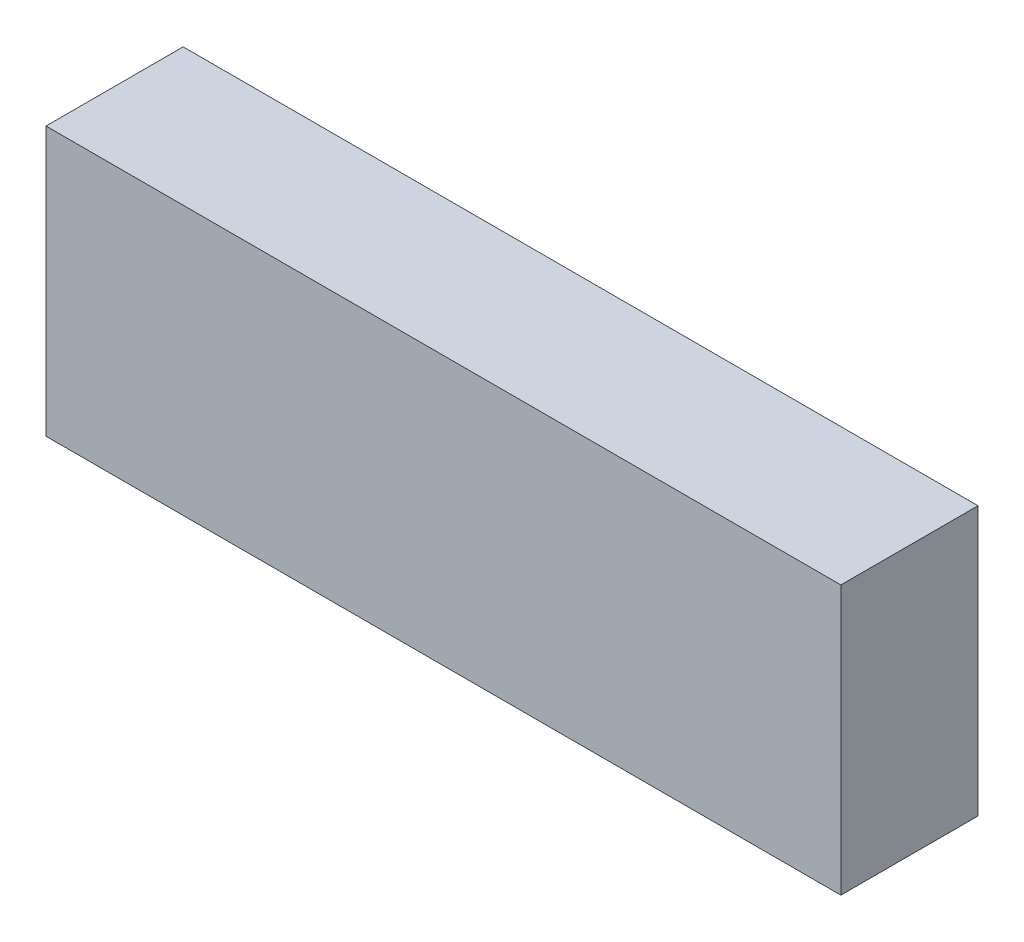
SolidWorks part; units mm, degrees
ref_plane "Front Plane" through (0, 0, 0) normal (0, 0, 1) x (1, 0, 0)
ref_plane "Top Plane" through (0, 0, 0) normal (0, 1, 0) x (1, 0, 0)
ref_plane "Right Plane" through (0, 0, 0) normal (1, 0, 0) x (0, 0, -1)
sketch "Sketch1" plane through (0, 0, 0) normal (0, 0, 1) x (1, 0, 0)
  line L1 (0, 0) -> (142, 0)
  line L2 (0, 0) -> (0, 48)
  line L3 (0, 48) -> (142, 48)
  line L4 (142, 0) -> (142, 48)
  dimension "D1" = 142
  dimension "D2" = 48
extrude "Boss-Extrude1" add sketch "Sketch1" along normal blind 24.5
